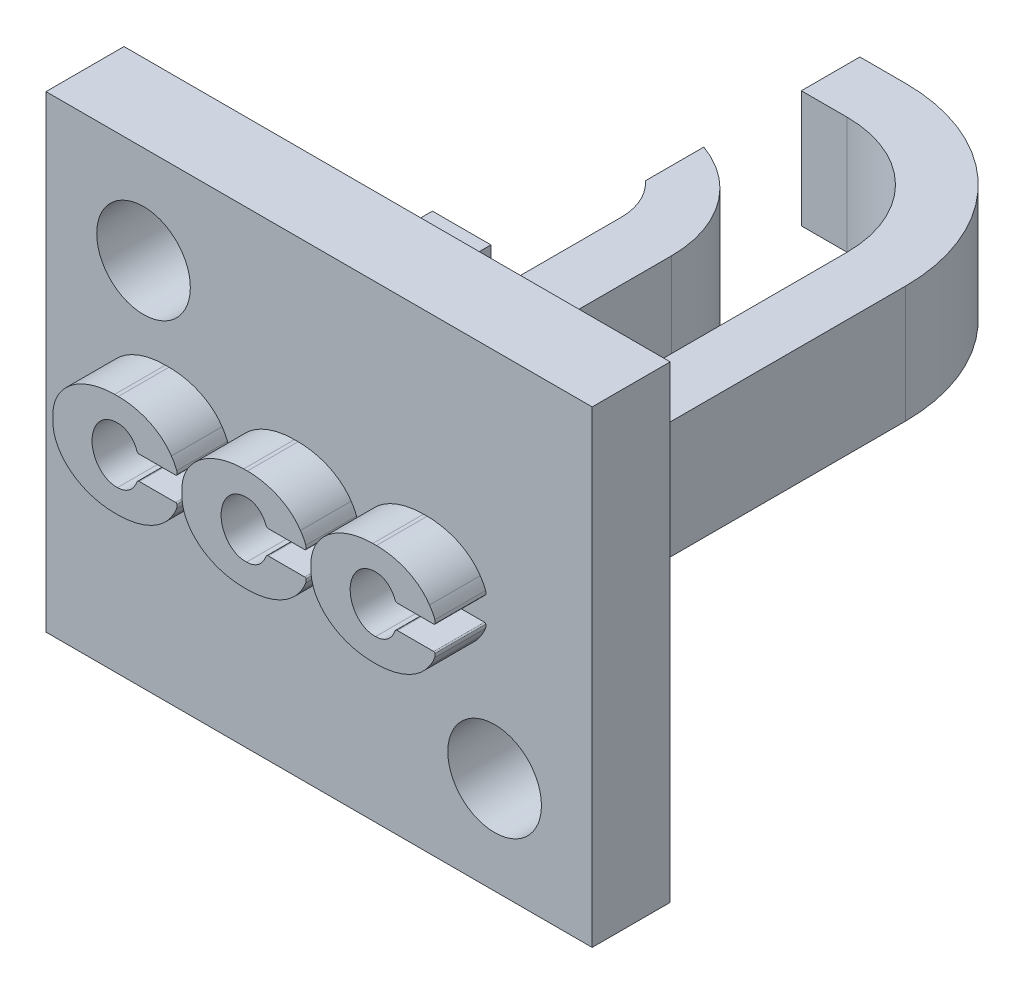
SolidWorks part; units mm, degrees
ref_plane "Front Plane" through (0, 0, 0) normal (0, 0, 1) x (1, 0, 0)
ref_plane "Top Plane" through (0, 0, 0) normal (0, 1, 0) x (1, 0, 0)
ref_plane "Right Plane" through (0, 0, 0) normal (1, 0, 0) x (0, 0, -1)
sketch "Sketch1" plane through (0, 0, 0) normal (0, 0, 1) x (1, 0, 0)
  line L1 (-7.5, 6) -> (7.5, 6)
  line L2 (-7.5, 6) -> (-7.5, -6)
  line L3 (-7.5, -6) -> (7.5, -6)
  line L4 (7.5, 6) -> (7.5, -6)
  line L5 (-7.5, 6) -> (7.5, -6) construction
  line L6 (-7.5, -6) -> (7.5, 6) construction
  point P0 (0, 0)
  dimension "D1" = 15
  dimension "D2" = 12
extrude "Boss-Extrude1" add sketch "Sketch1" along normal blind 2
sketch "Sketch2" plane through (0, 0, 2) normal (0, 0, 1) x (1, 0, 0)
  line L0 (-0.5005, 0.4472) -> (0.4353, 0.4472)
  line L1 (-1.0379, 1.458) -> (-1.1315, 1.458)
  line L2 (-2.7171, 0.2068) -> (-2.7171, 0.0767)
  line L3 (-1.1315, -1.1745) -> (-1.0379, -1.1745)
  line L4 (0.4308, -0.1598) -> (-0.5005, -0.1598)
  line L5 (-3.8088, 0.4472) -> (-2.873, 0.4472)
  line L6 (-4.3462, 1.458) -> (-4.4398, 1.458)
  line L7 (-6.0254, 0.2068) -> (-6.0254, 0.0767)
  line L8 (-4.4398, -1.1745) -> (-4.3462, -1.1745)
  line L9 (-2.8775, -0.1598) -> (-3.8088, -0.1598)
  line L10 (2.8078, 0.4472) -> (3.7437, 0.4472)
  line L11 (2.2704, 1.458) -> (2.1768, 1.458)
  line L12 (0.5912, 0.2068) -> (0.5912, 0.0767)
  line L13 (2.1768, -1.1745) -> (2.2704, -1.1745)
  line L14 (3.7391, -0.1598) -> (2.8078, -0.1598)
  arc A0 (-0.5622, 0.4908) -> (-0.5005, 0.4472) centre (-0.5005, 0.5126) ccw
  arc A1 (0.4353, 0.4472) -> (0.4646, 0.4721) centre (0.4309, 0.4821) ccw
  arc A2 (0.4646, 0.4721) -> (0.4604, 0.5595) centre (0.284, 0.5073) ccw
  arc A3 (0.4604, 0.5595) -> (0.3232, 0.8168) centre (-0.6216, 0.148) ccw
  arc A4 (0.3232, -0.5333) -> (0.4557, -0.287) centre (-0.6122, 0.1283) ccw
  arc A5 (0.4557, -0.287) -> (0.4655, -0.189) centre (0.2842, -0.2203) ccw
  arc A6 (0.4655, -0.189) -> (0.4308, -0.1598) centre (0.4308, -0.195) ccw
  arc A7 (-0.5005, -0.1598) -> (-0.5622, -0.2034) centre (-0.5005, -0.2253) ccw
  arc A8 (-3.8705, 0.4908) -> (-3.8088, 0.4472) centre (-3.8088, 0.5126) ccw
  arc A9 (-2.873, 0.4472) -> (-2.8437, 0.4721) centre (-2.8774, 0.4821) ccw
  arc A10 (-2.8437, 0.4721) -> (-2.8479, 0.5595) centre (-3.0243, 0.5073) ccw
  arc A11 (-2.8479, 0.5595) -> (-2.9851, 0.8168) centre (-3.9299, 0.148) ccw
  arc A12 (-2.9851, -0.5333) -> (-2.8527, -0.287) centre (-3.9205, 0.1283) ccw
  arc A13 (-2.8527, -0.287) -> (-2.8428, -0.189) centre (-3.0241, -0.2203) ccw
  arc A14 (-2.8428, -0.189) -> (-2.8775, -0.1598) centre (-2.8775, -0.195) ccw
  arc A15 (-3.8088, -0.1598) -> (-3.8705, -0.2034) centre (-3.8088, -0.2253) ccw
  arc A16 (2.7461, 0.4908) -> (2.8078, 0.4472) centre (2.8078, 0.5126) ccw
  arc A17 (3.7437, 0.4472) -> (3.7729, 0.4721) centre (3.7392, 0.4821) ccw
  arc A18 (3.7729, 0.4721) -> (3.7687, 0.5595) centre (3.5923, 0.5073) ccw
  arc A19 (3.7687, 0.5595) -> (3.6315, 0.8168) centre (2.6867, 0.148) ccw
  arc A20 (3.6315, -0.5333) -> (3.764, -0.287) centre (2.6961, 0.1283) ccw
  arc A21 (3.764, -0.287) -> (3.7738, -0.189) centre (3.5925, -0.2203) ccw
  arc A22 (3.7738, -0.189) -> (3.7391, -0.1598) centre (3.7391, -0.195) ccw
  arc A23 (2.8078, -0.1598) -> (2.7461, -0.2034) centre (2.8078, -0.2253) ccw
  ellipse E0 centre (-1.0904, 0.1419) end of major axis (-1.0868, -0.5752) minor radius 0.6209 (-1.1185, 0.8583) -> (-1.0587, -0.5743) ccw
  ellipse E1 centre (-1.1465, 0.1419) end of major axis (-1.4291, -0.5397) minor radius 0.6039 (-0.5622, 0.4908) -> (-1.1185, 0.8583) ccw
  ellipse E2 centre (-1.1599, 0.1563) end of major axis (0.4829, 0.4015) minor radius 1.2925 (0.3232, 0.8168) -> (-1.0379, 1.458) ccw
  ellipse E3 centre (-1.0691, 0.1576) end of major axis (-2.714, 0.287) minor radius 1.2979 (-1.1315, 1.458) -> (-2.7171, 0.2068) ccw
  ellipse E4 centre (-1.0691, 0.1259) end of major axis (0.5758, 0.2553) minor radius 1.2979 (-2.7171, 0.0767) -> (-1.1315, -1.1745) ccw
  ellipse E5 centre (-1.1599, 0.1272) end of major axis (-2.8027, 0.3723) minor radius 1.2925 (-1.0379, -1.1745) -> (0.3232, -0.5333) ccw
  ellipse E6 centre (-1.1465, 0.1455) end of major axis (-0.8639, -0.5361) minor radius 0.6039 (-1.0587, -0.5743) -> (-0.5622, -0.2034) ccw
  ellipse E7 centre (-4.4548, 0.1419) end of major axis (-4.1722, 0.8235) minor radius 0.6039 (-3.8705, 0.4908) -> (-4.4268, 0.8583) ccw
  ellipse E8 centre (-4.4682, 0.1563) end of major axis (-2.8254, 0.4015) minor radius 1.2925 (-2.9851, 0.8168) -> (-4.3462, 1.458) ccw
  ellipse E9 centre (-4.3774, 0.1576) end of major axis (-6.0223, 0.287) minor radius 1.2979 (-4.4398, 1.458) -> (-6.0254, 0.2068) ccw
  ellipse E10 centre (-4.3774, 0.1259) end of major axis (-6.0223, -0.0034) minor radius 1.2979 (-6.0254, 0.0767) -> (-4.4398, -1.1745) ccw
  ellipse E11 centre (-4.4682, 0.1272) end of major axis (-6.111, 0.3723) minor radius 1.2925 (-4.3462, -1.1745) -> (-2.9851, -0.5333) ccw
  ellipse E12 centre (-4.4548, 0.1455) end of major axis (-4.7375, 0.8271) minor radius 0.6039 (-4.367, -0.5743) -> (-3.8705, -0.2034) ccw
  ellipse E13 centre (-4.3987, 0.1419) end of major axis (-4.3951, -0.5752) minor radius 0.6209 (-4.4268, 0.8583) -> (-4.367, -0.5743) ccw
  ellipse E14 centre (2.2179, 0.1419) end of major axis (2.2143, 0.859) minor radius 0.6209 (2.1899, 0.8583) -> (2.2496, -0.5743) ccw
  ellipse E15 centre (2.1618, 0.1419) end of major axis (1.8792, -0.5397) minor radius 0.6039 (2.7461, 0.4908) -> (2.1899, 0.8583) ccw
  ellipse E16 centre (2.1484, 0.1563) end of major axis (3.7912, 0.4015) minor radius 1.2925 (3.6315, 0.8168) -> (2.2704, 1.458) ccw
  ellipse E17 centre (2.2392, 0.1576) end of major axis (0.5943, 0.287) minor radius 1.2979 (2.1768, 1.458) -> (0.5912, 0.2068) ccw
  ellipse E18 centre (2.2392, 0.1259) end of major axis (3.8841, 0.2553) minor radius 1.2979 (0.5912, 0.0767) -> (2.1768, -1.1745) ccw
  ellipse E19 centre (2.1484, 0.1272) end of major axis (0.5056, 0.3723) minor radius 1.2925 (2.2704, -1.1745) -> (3.6315, -0.5333) ccw
  ellipse E20 centre (2.1618, 0.1455) end of major axis (1.8792, 0.8271) minor radius 0.6039 (2.2496, -0.5743) -> (2.7461, -0.2034) ccw
extrude "Boss-Extrude2" add sketch "Sketch2" along normal blind 2
sketch "Sketch3" plane through (0, 0, 0) normal (0, 1, 0) x (1, 0, 0)
  line L0 (7.5, 0) -> (-7.5, 0) construction
  line L1 (1.8337, 0) -> (3.3337, 0)
  line L2 (1.8337, 0) -> (1.8337, 12.2)
  line L3 (-3.644, -2) -> (-3.644, 5.3789) construction
  line L4 (3.3337, 0) -> (3.3337, 13.7)
  line L5 (-4.394, 0) -> (-2.894, 0)
  line L6 (-4.394, 0) -> (-4.394, 4.8)
  line L7 (-1.0877, -2) -> (-1.0877, 4.6797) construction
  line L8 (-2.894, 0) -> (-2.894, 4.8)
  line L9 (-2.894, 4.8) -> (-4.394, 4.8)
  line L10 (-1.8377, 0) -> (-0.3377, 0)
  line L11 (7.5, -2) -> (-7.5, -2) construction
  line L13 (-1.8377, 0) -> (-1.8377, 8.2)
  line L14 (2.5837, -2) -> (2.5837, 2.787) construction
  line L15 (-0.3377, 0) -> (-0.3377, 9.7)
  line L16 (-0.3377, 9.7) -> (-2.3377, 9.7)
  line L17 (-2.3377, 13.7) -> (3.3337, 13.7)
  line L18 (-1.8377, 8.2) -> (-2.3377, 8.2)
  line L19 (-2.3377, 9.7) -> (-2.3377, 8.2)
  line L20 (-2.3377, 13.7) -> (-2.3377, 12.2)
  line L21 (-2.3377, 12.2) -> (1.8337, 12.2)
  dimension "D1" = 1.5
  dimension "D2" = 4.8
  dimension "D3" = 1.5
  dimension "D4" = 1.5
  dimension "D5" = 8.2
  dimension "D6" = 1.5
  dimension "D7" = 2.5
  dimension "D8" = 1.5
  dimension "D9" = 0.5
  dimension "D10" = 1.0877
  dimension "D11" = 2.5837
  dimension "D12" = 3.644
extrude "Boss-Extrude3" add sketch "Sketch3" along normal mid plane 3
fillet "Fillet3" radius 1.5 1 edges at (-1.8377, 0, -8.2)
fillet "Fillet4" radius 3 1 edges at (-0.3377, 0, -9.7)
fillet "Fillet5" radius 3 1 edges at (1.8337, 0, -12.2)
fillet "Fillet6" radius 4.5 1 edges at (3.3337, 0, -13.7)
sketch "Sketch4" plane through (7.5, 0, 0) normal (1, 0, 0) x (0, 0, -1)
  line L4 (0, -6) -> (0, 6)
  line L5 (0, 6) -> (-2, 6)
  line L6 (-2, 6) -> (-2, -6)
  line L7 (-2, -6) -> (0, -6)
  line L8 (0, -6) -> (0, 6)
  line L9 (0, 6) -> (-2, 6)
  line L10 (-2, 6) -> (-2, -6)
  line L11 (-2, -6) -> (0, -6)
  dimension "D1" = 0
extrude "Cut-Extrude1" cut sketch "Sketch4" against normal blind 1
sketch "Sketch5" plane through (0, 0, 0) normal (0, 0, -1) x (-1, 0, 0)
  line L0 (-6.5, -6) -> (-6.5, 6) construction
  line L1 (7.5, -6) -> (-6.5, -6) construction
  line L2 (7.5, 6) -> (7.5, -6) construction
  line L3 (-6.5, 6) -> (7.5, 6) construction
  circle A0 centre (-4, -3.5) radius 1.2
  circle A1 centre (5, 3.5) radius 1.2
  dimension "D1" = 2.4
  dimension "D2" = 2.5
  dimension "D3" = 2.5
  dimension "D4" = 2.5
  dimension "D5" = 2.5
extrude "Cut-Extrude2" cut sketch "Sketch5" against normal through all
sketch "Sketch6" plane through (0, 0, 4) normal (0, 0, 1) x (1, 0, 0)
  line L0 (-0.5005, 0.4472) -> (0.4353, 0.4472) construction
  line L1 (-1.0379, 1.458) -> (-1.1315, 1.458) construction
  line L2 (-2.7171, 0.2068) -> (-2.7171, 0.0767) construction
  line L3 (-1.1315, -1.1745) -> (-1.0379, -1.1745) construction
  line L4 (0.4308, -0.1598) -> (-0.5005, -0.1598) construction
  line L5 (-3.8088, 0.4472) -> (-2.873, 0.4472)
  line L6 (-4.3462, 1.458) -> (-4.4398, 1.458)
  line L7 (-6.0254, 0.2068) -> (-6.0254, 0.0767)
  line L8 (-4.4398, -1.1745) -> (-4.3462, -1.1745)
  line L9 (-2.8775, -0.1598) -> (-3.8088, -0.1598)
  line L10 (-3.8088, 0.4472) -> (-2.873, 0.4472)
  line L11 (-4.3462, 1.458) -> (-4.4398, 1.458)
  line L12 (-6.0254, 0.2068) -> (-6.0254, 0.0767)
  line L13 (-4.4398, -1.1745) -> (-4.3462, -1.1745)
  line L14 (-2.8775, -0.1598) -> (-3.8088, -0.1598)
  line L15 (2.8078, 0.4472) -> (3.7437, 0.4472) construction
  line L16 (2.2704, 1.458) -> (2.1768, 1.458) construction
  line L17 (0.5912, 0.2068) -> (0.5912, 0.0767) construction
  line L18 (2.1768, -1.1745) -> (2.2704, -1.1745) construction
  line L19 (3.7391, -0.1598) -> (2.8078, -0.1598) construction
  line L20 (-0.5005, 0.4472) -> (0.4353, 0.4472)
  line L21 (-1.0379, 1.458) -> (-1.1315, 1.458)
  line L22 (-2.7171, 0.2068) -> (-2.7171, 0.0767)
  line L23 (-1.1315, -1.1745) -> (-1.0379, -1.1745)
  line L24 (0.4308, -0.1598) -> (-0.5005, -0.1598)
  line L25 (2.8078, 0.4472) -> (3.7437, 0.4472)
  line L26 (2.2704, 1.458) -> (2.1768, 1.458)
  line L27 (0.5912, 0.2068) -> (0.5912, 0.0767)
  line L28 (2.1768, -1.1745) -> (2.2704, -1.1745)
  line L29 (3.7391, -0.1598) -> (2.8078, -0.1598)
  arc A0 (-0.5622, 0.4908) -> (-0.5005, 0.4472) centre (-0.5005, 0.5126) ccw construction
  arc A1 (0.4353, 0.4472) -> (0.4646, 0.4721) centre (0.4309, 0.4821) ccw construction
  arc A2 (0.4646, 0.4721) -> (0.4604, 0.5595) centre (0.284, 0.5073) ccw construction
  arc A3 (0.4604, 0.5595) -> (0.3232, 0.8168) centre (-0.6216, 0.148) ccw construction
  arc A4 (0.3232, -0.5333) -> (0.4557, -0.287) centre (-0.6122, 0.1283) ccw construction
  arc A5 (0.4557, -0.287) -> (0.4655, -0.189) centre (0.2842, -0.2203) ccw construction
  arc A6 (0.4655, -0.189) -> (0.4308, -0.1598) centre (0.4308, -0.195) ccw construction
  arc A7 (-0.5005, -0.1598) -> (-0.5622, -0.2034) centre (-0.5005, -0.2253) ccw construction
  arc A8 (-3.8705, 0.4908) -> (-3.8088, 0.4472) centre (-3.8088, 0.5126) ccw
  arc A9 (-2.873, 0.4472) -> (-2.8437, 0.4721) centre (-2.8774, 0.4821) ccw
  arc A10 (-2.8437, 0.4721) -> (-2.8479, 0.5595) centre (-3.0243, 0.5073) ccw
  arc A11 (-2.8479, 0.5595) -> (-2.9851, 0.8168) centre (-3.9299, 0.148) ccw
  arc A12 (-2.9851, -0.5333) -> (-2.8527, -0.287) centre (-3.9205, 0.1283) ccw
  arc A13 (-2.8527, -0.287) -> (-2.8428, -0.189) centre (-3.0241, -0.2203) ccw
  arc A14 (-2.8428, -0.189) -> (-2.8775, -0.1598) centre (-2.8775, -0.195) ccw
  arc A15 (-3.8088, -0.1598) -> (-3.8705, -0.2034) centre (-3.8088, -0.2253) ccw
  arc A16 (-3.8705, 0.4908) -> (-3.8088, 0.4472) centre (-3.8088, 0.5126) ccw
  arc A17 (-2.873, 0.4472) -> (-2.8437, 0.4721) centre (-2.8774, 0.4821) ccw
  arc A18 (-2.8437, 0.4721) -> (-2.8479, 0.5595) centre (-3.0243, 0.5073) ccw
  arc A19 (-2.8479, 0.5595) -> (-2.9851, 0.8168) centre (-3.9299, 0.148) ccw
  arc A20 (-2.9851, -0.5333) -> (-2.8527, -0.287) centre (-3.9205, 0.1283) ccw
  arc A21 (-2.8527, -0.287) -> (-2.8428, -0.189) centre (-3.0241, -0.2203) ccw
  arc A22 (-2.8428, -0.189) -> (-2.8775, -0.1598) centre (-2.8775, -0.195) ccw
  arc A23 (-3.8088, -0.1598) -> (-3.8705, -0.2034) centre (-3.8088, -0.2253) ccw
  arc A24 (2.7461, 0.4908) -> (2.8078, 0.4472) centre (2.8078, 0.5126) ccw construction
  arc A25 (3.7437, 0.4472) -> (3.7729, 0.4721) centre (3.7392, 0.4821) ccw construction
  arc A26 (3.7729, 0.4721) -> (3.7687, 0.5595) centre (3.5923, 0.5073) ccw construction
  arc A27 (3.7687, 0.5595) -> (3.6315, 0.8168) centre (2.6867, 0.148) ccw construction
  arc A28 (3.6315, -0.5333) -> (3.764, -0.287) centre (2.6961, 0.1283) ccw construction
  arc A29 (3.764, -0.287) -> (3.7738, -0.189) centre (3.5925, -0.2203) ccw construction
  arc A30 (3.7738, -0.189) -> (3.7391, -0.1598) centre (3.7391, -0.195) ccw construction
  arc A31 (2.8078, -0.1598) -> (2.7461, -0.2034) centre (2.8078, -0.2253) ccw construction
  arc A32 (-0.5622, 0.4908) -> (-0.5005, 0.4472) centre (-0.5005, 0.5126) ccw
  arc A33 (0.4353, 0.4472) -> (0.4646, 0.4721) centre (0.4309, 0.4821) ccw
  arc A34 (0.4646, 0.4721) -> (0.4604, 0.5595) centre (0.284, 0.5073) ccw
  arc A35 (0.4604, 0.5595) -> (0.3232, 0.8168) centre (-0.6216, 0.148) ccw
  arc A36 (0.3232, -0.5333) -> (0.4557, -0.287) centre (-0.6122, 0.1283) ccw
  arc A37 (0.4557, -0.287) -> (0.4655, -0.189) centre (0.2842, -0.2203) ccw
  arc A38 (0.4655, -0.189) -> (0.4308, -0.1598) centre (0.4308, -0.195) ccw
  arc A39 (-0.5005, -0.1598) -> (-0.5622, -0.2034) centre (-0.5005, -0.2253) ccw
  arc A40 (2.7461, 0.4908) -> (2.8078, 0.4472) centre (2.8078, 0.5126) ccw
  arc A41 (3.7437, 0.4472) -> (3.7729, 0.4721) centre (3.7392, 0.4821) ccw
  arc A42 (3.7729, 0.4721) -> (3.7687, 0.5595) centre (3.5923, 0.5073) ccw
  arc A43 (3.7687, 0.5595) -> (3.6315, 0.8168) centre (2.6867, 0.148) ccw
  arc A44 (3.6315, -0.5333) -> (3.764, -0.287) centre (2.6961, 0.1283) ccw
  arc A45 (3.764, -0.287) -> (3.7738, -0.189) centre (3.5925, -0.2203) ccw
  arc A46 (3.7738, -0.189) -> (3.7391, -0.1598) centre (3.7391, -0.195) ccw
  arc A47 (2.8078, -0.1598) -> (2.7461, -0.2034) centre (2.8078, -0.2253) ccw
  ellipse E0 centre (-1.1465, 0.1419) end of major axis (-0.8639, 0.8235) minor radius 0.6039 (-0.5622, 0.4908) -> (-1.1185, 0.8583) ccw construction
  ellipse E1 centre (-1.1599, 0.1563) end of major axis (0.4829, 0.4015) minor radius 1.2925 (0.3232, 0.8168) -> (-1.0379, 1.458) ccw construction
  ellipse E2 centre (-1.0691, 0.1576) end of major axis (-2.714, 0.287) minor radius 1.2979 (-1.1315, 1.458) -> (-2.7171, 0.2068) ccw construction
  ellipse E3 centre (-1.0691, 0.1259) end of major axis (0.5758, 0.2553) minor radius 1.2979 (-2.7171, 0.0767) -> (-1.1315, -1.1745) ccw construction
  ellipse E4 centre (-1.1599, 0.1272) end of major axis (-2.8027, 0.3723) minor radius 1.2925 (-1.0379, -1.1745) -> (0.3232, -0.5333) ccw construction
  ellipse E5 centre (-1.1465, 0.1455) end of major axis (-0.8639, -0.5361) minor radius 0.6039 (-1.0587, -0.5743) -> (-0.5622, -0.2034) ccw construction
  ellipse E6 centre (-1.0904, 0.1419) end of major axis (-1.0868, -0.5752) minor radius 0.6209 (-1.1185, 0.8583) -> (-1.0587, -0.5743) ccw construction
  ellipse E7 centre (-4.4548, 0.1419) end of major axis (-4.7375, -0.5397) minor radius 0.6039 (-3.8705, 0.4908) -> (-4.4268, 0.8583) ccw
  ellipse E8 centre (-4.4682, 0.1563) end of major axis (-2.8254, 0.4015) minor radius 1.2925 (-2.9851, 0.8168) -> (-4.3462, 1.458) ccw
  ellipse E9 centre (-4.3774, 0.1576) end of major axis (-6.0223, 0.287) minor radius 1.2979 (-4.4398, 1.458) -> (-6.0254, 0.2068) ccw
  ellipse E10 centre (-4.3774, 0.1259) end of major axis (-6.0223, -0.0034) minor radius 1.2979 (-6.0254, 0.0767) -> (-4.4398, -1.1745) ccw
  ellipse E11 centre (-4.4682, 0.1272) end of major axis (-6.111, 0.3723) minor radius 1.2925 (-4.3462, -1.1745) -> (-2.9851, -0.5333) ccw
  ellipse E12 centre (-4.4548, 0.1455) end of major axis (-4.1722, -0.5361) minor radius 0.6039 (-4.367, -0.5743) -> (-3.8705, -0.2034) ccw
  ellipse E13 centre (-4.3987, 0.1419) end of major axis (-4.3951, -0.5752) minor radius 0.6209 (-4.4268, 0.8583) -> (-4.367, -0.5743) ccw
  ellipse E14 centre (-4.4548, 0.1419) end of major axis (-4.7375, -0.5397) minor radius 0.6039 (-3.8705, 0.4908) -> (-4.4268, 0.8583) ccw
  ellipse E15 centre (-4.4682, 0.1563) end of major axis (-2.8254, 0.4015) minor radius 1.2925 (-2.9851, 0.8168) -> (-4.3462, 1.458) ccw
  ellipse E16 centre (-4.3774, 0.1576) end of major axis (-6.0223, 0.287) minor radius 1.2979 (-4.4398, 1.458) -> (-6.0254, 0.2068) ccw
  ellipse E17 centre (-4.3774, 0.1259) end of major axis (-6.0223, -0.0034) minor radius 1.2979 (-6.0254, 0.0767) -> (-4.4398, -1.1745) ccw
  ellipse E18 centre (-4.4682, 0.1272) end of major axis (-6.111, 0.3723) minor radius 1.2925 (-4.3462, -1.1745) -> (-2.9851, -0.5333) ccw
  ellipse E19 centre (-4.4548, 0.1455) end of major axis (-4.1722, -0.5361) minor radius 0.6039 (-4.367, -0.5743) -> (-3.8705, -0.2034) ccw
  ellipse E20 centre (-4.3987, 0.1419) end of major axis (-4.3951, -0.5752) minor radius 0.6209 (-4.4268, 0.8583) -> (-4.367, -0.5743) ccw
  ellipse E21 centre (2.1618, 0.1419) end of major axis (1.8792, -0.5397) minor radius 0.6039 (2.7461, 0.4908) -> (2.1899, 0.8583) ccw construction
  ellipse E22 centre (2.1484, 0.1563) end of major axis (3.7912, 0.4015) minor radius 1.2925 (3.6315, 0.8168) -> (2.2704, 1.458) ccw construction
  ellipse E23 centre (2.2392, 0.1576) end of major axis (0.5943, 0.287) minor radius 1.2979 (2.1768, 1.458) -> (0.5912, 0.2068) ccw construction
  ellipse E24 centre (2.2392, 0.1259) end of major axis (3.8841, 0.2553) minor radius 1.2979 (0.5912, 0.0767) -> (2.1768, -1.1745) ccw construction
  ellipse E25 centre (2.1484, 0.1272) end of major axis (0.5056, 0.3723) minor radius 1.2925 (2.2704, -1.1745) -> (3.6315, -0.5333) ccw construction
  ellipse E26 centre (2.1618, 0.1455) end of major axis (2.4444, -0.5361) minor radius 0.6039 (2.2496, -0.5743) -> (2.7461, -0.2034) ccw construction
  ellipse E27 centre (2.2179, 0.1419) end of major axis (2.2215, -0.5752) minor radius 0.6209 (2.1899, 0.8583) -> (2.2496, -0.5743) ccw construction
  ellipse E28 centre (-1.1465, 0.1419) end of major axis (-1.4291, -0.5397) minor radius 0.6039 (-0.5622, 0.4908) -> (-1.1185, 0.8583) ccw
  ellipse E29 centre (-1.1599, 0.1563) end of major axis (0.4829, 0.4015) minor radius 1.2925 (0.3232, 0.8168) -> (-1.0379, 1.458) ccw
  ellipse E30 centre (-1.0691, 0.1576) end of major axis (-2.714, 0.287) minor radius 1.2979 (-1.1315, 1.458) -> (-2.7171, 0.2068) ccw
  ellipse E31 centre (-1.0691, 0.1259) end of major axis (0.5758, 0.2553) minor radius 1.2979 (-2.7171, 0.0767) -> (-1.1315, -1.1745) ccw
  ellipse E32 centre (-1.1599, 0.1272) end of major axis (-2.8027, 0.3723) minor radius 1.2925 (-1.0379, -1.1745) -> (0.3232, -0.5333) ccw
  ellipse E33 centre (-1.1465, 0.1455) end of major axis (-0.8639, -0.5361) minor radius 0.6039 (-1.0587, -0.5743) -> (-0.5622, -0.2034) ccw
  ellipse E34 centre (-1.0904, 0.1419) end of major axis (-1.0868, -0.5752) minor radius 0.6209 (-1.1185, 0.8583) -> (-1.0587, -0.5743) ccw
  ellipse E35 centre (2.1618, 0.1419) end of major axis (1.8792, -0.5397) minor radius 0.6039 (2.7461, 0.4908) -> (2.1899, 0.8583) ccw
  ellipse E36 centre (2.1484, 0.1563) end of major axis (3.7912, 0.4015) minor radius 1.2925 (3.6315, 0.8168) -> (2.2704, 1.458) ccw
  ellipse E37 centre (2.2392, 0.1576) end of major axis (0.5943, 0.287) minor radius 1.2979 (2.1768, 1.458) -> (0.5912, 0.2068) ccw
  ellipse E38 centre (2.2392, 0.1259) end of major axis (3.8841, 0.2553) minor radius 1.2979 (0.5912, 0.0767) -> (2.1768, -1.1745) ccw
  ellipse E39 centre (2.1484, 0.1272) end of major axis (0.5056, 0.3723) minor radius 1.2925 (2.2704, -1.1745) -> (3.6315, -0.5333) ccw
  ellipse E40 centre (2.1618, 0.1455) end of major axis (2.4444, -0.5361) minor radius 0.6039 (2.2496, -0.5743) -> (2.7461, -0.2034) ccw
  ellipse E41 centre (2.2179, 0.1419) end of major axis (2.2215, -0.5752) minor radius 0.6209 (2.1899, 0.8583) -> (2.2496, -0.5743) ccw
  dimension "D1" = 0
extrude "Cut-Extrude3" cut sketch "Sketch6" against normal blind 0.7
